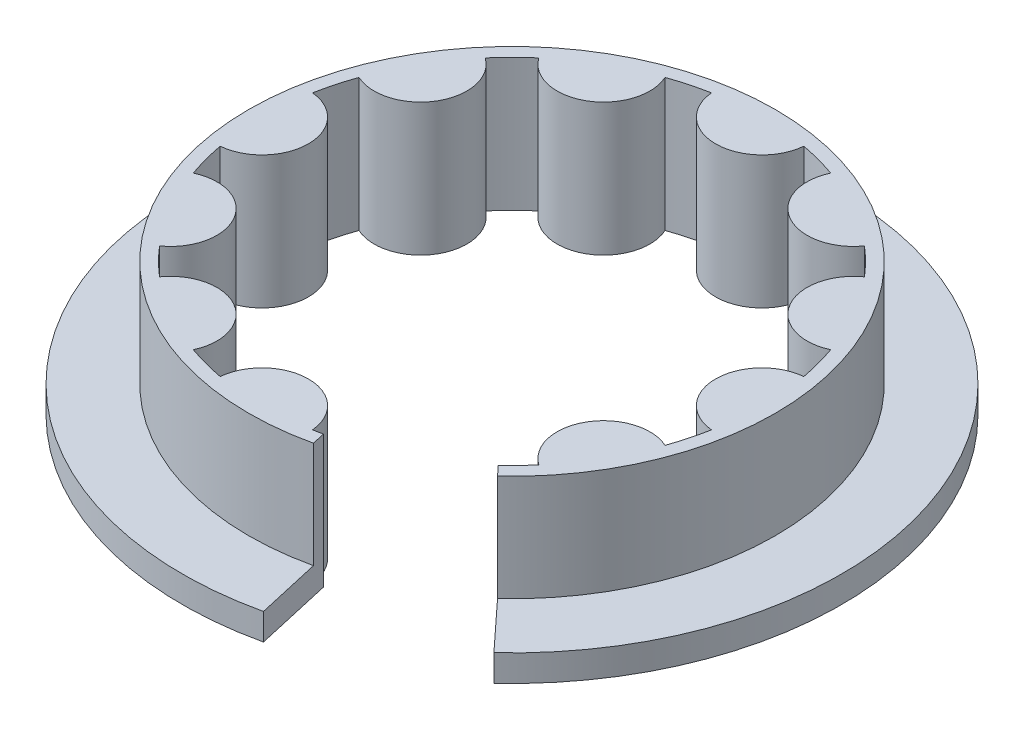
SolidWorks part; units mm, degrees
ref_plane "Front Plane" through (0, 0, 0) normal (0, 0, 1) x (1, 0, 0)
ref_plane "Top Plane" through (0, 0, 0) normal (0, 1, 0) x (1, 0, 0)
ref_plane "Right Plane" through (0, 0, 0) normal (1, 0, 0) x (0, 0, -1)
sketch "Sketch1" plane through (0, 0, 0) normal (0, 1, 0) x (1, 0, 0)
  circle A1 centre (-10, 0) radius 1.75
  circle A2 centre (-8.737, 4.7137) radius 1.75
  circle A3 centre (-5.2863, 8.1644) radius 1.75
  circle A4 centre (-0.5726, 9.4274) radius 1.75
  circle A5 centre (4.1412, 8.1644) radius 1.75
  circle A6 centre (7.5918, 4.7137) radius 1.75
  circle A7 centre (8.8549, 0) radius 1.75
  circle A8 centre (7.5918, -4.7137) radius 1.75
  circle A9 centre (4.1412, -8.1644) radius 1.75
  circle A10 centre (-0.5726, -9.4274) radius 1.75
  circle A11 centre (-5.2863, -8.1644) radius 1.75
  circle A12 centre (-8.737, -4.7137) radius 1.75
  circle A13 centre (-0.5726, 0) radius 9.4274
  circle A14 centre (-0.5726, 0) radius 12.4274
  dimension "D1" = 3
  dimension "D2" = 3.5
  dimension "D4" = 4.88
  dimension "D3" = 12
extrude "Boss-Extrude1" add sketch "Sketch1" along normal blind 5 contours A14 A13 A10 A11 A12 A1 A2 A3 A4 A5 A6 A7 A8 A9 | A13 A12 | A12 A13 | A1 A13 | A13 A1 | A2 A13 | A13 A2 | A3 A13 | A13 A3 | A4 A13 | A13 A4 | A5 A13 | A13 A5 | A6 A13 | A13 A6 | A7 A13 | A13 A7 | A8 A13 | A13 A8 | A9 A13 | A13 A9 | A10 A13 | A13 A10 | A11 A13 | A13 A11 region at (-9.2288, 0, 0) region at (-10.7127, 0, 0) region at (-8.0691, 0, -4.3281) region at (-9.3542, 0, -5.0701) region at (-9.3542, 0, 5.0701) region at (-8.0691, 0, 4.3281) region at (-4.9007, 0, -7.4965) region at (-5.6426, 0, -8.7816) region at (-5.6426, 0, 8.7816) region at (-4.9007, 0, 7.4965) region at (-0.5726, 0, -8.6562) region at (-0.5726, 0, -10.1401) region at (-0.5726, 0, 10.1401) region at (-0.5726, 0, 8.6562) region at (3.7556, 0, -7.4965) region at (4.4975, 0, -8.7816) region at (4.4975, 0, 8.7816) region at (3.7556, 0, 7.4965) region at (6.924, 0, -4.3281) region at (8.2091, 0, -5.0701) region at (8.2091, 0, 5.0701) region at (6.924, 0, 4.3281) region at (8.0837, 0, 0) region at (9.5676, 0, 0) region at (-12.6485, 0, 0)
sketch "Sketch3" plane through (0, 5, 0) normal (0, 1, 0) x (1, 0, 0)
  line L0 (-0.5726, 0) -> (2.1749, -12.1199)
  line L1 (-0.5726, 0) -> (7.8668, -9.1224)
  circle A0 centre (-0.5726, 0) radius 9.9274
  circle A1 centre (-0.5726, 0) radius 9.4274 construction
  circle A2 centre (-0.5726, 0) radius 12.4274
  arc M5 (2.5509, -8.895) -> (1.1699, -9.265) centre (-0.5726, 0) cw
  arc M27 (6.5799, -6.1415) -> (5.5689, -7.1525) centre (-0.5726, 0) cw
  arc M28 (5.5689, -7.1525) -> (2.5509, -8.895) centre (4.1412, -8.1644) ccw
  circle M29 centre (-0.5726, 0) radius 12.4274
  dimension "D1" = 0.5
  dimension "D2" = 30
extrude "Cut-Extrude1" cut sketch "Sketch3" against normal offset from surface (4 mm away) 1 contours A0 L1 L0 M29 | A0 L0 L1 M29 region at (4.5979, 5, 9.818) region at (1.5557, 5, 10.9786) up to face at (-0.5726, 0, 0)
extrude "Cut-Extrude2" cut sketch "Sketch3<3>" against normal through all contours A0 L0 L1 M29 | L0 A0 L1 M27 M28 M5 region at (3.8019, 5, 7.8402) region at (4.5979, 5, 9.818)
sketch "Sketch3<3>" plane through (0, 5, 0) normal (0, 1, 0) x (1, 0, 0) same geometry as "Sketch3"
equation "\"HOLE_SIZE\"= 3.5mm"
equation "\"DIST\"= 4.88mm"
